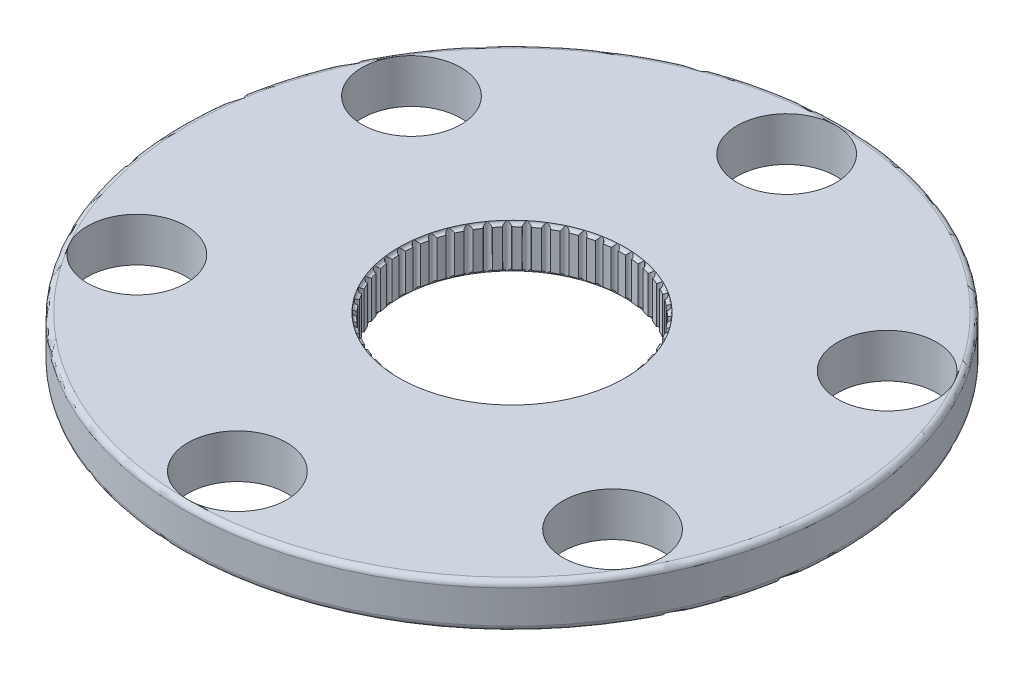
SolidWorks part; units mm, degrees
ref_plane "Front Plane" through (0, 0, 0) normal (0, 0, 1) x (1, 0, 0)
ref_plane "Top Plane" through (0, 0, 0) normal (0, 1, 0) x (1, 0, 0)
ref_plane "Right Plane" through (0, 0, 0) normal (1, 0, 0) x (0, 0, -1)
sketch "Sketch2" plane through (0, 0, 0) normal (0, 1, 0) x (1, 0, 0)
  line L0 (0, 73.1777) -> (0, -72.5679) construction
  line L1 (-73.7875, 0) -> (64.0305, 0) construction
  circle A0 centre (0, 0) radius 150
  circle A1 centre (0, 0) radius 50
  circle A2 centre (0, 125) radius 22.5
  circle A3 centre (108.2532, 62.5) radius 22.5
  circle A4 centre (108.2532, -62.5) radius 22.5
  circle A5 centre (0, -125) radius 22.5
  circle A6 centre (-108.2532, -62.5) radius 22.5
  circle A7 centre (-108.2532, 62.5) radius 22.5
  point P23 (0, 0)
  dimension "D1" = 100
  dimension "D2" = 300
  dimension "D3" = 45
  dimension "D4" = 125
  dimension "D5" = 6
extrude "Boss-Extrude1" add sketch "Sketch2" along normal mid plane 20
sketch "Sketch3" plane through (0, 0, 0) normal (1, 0, 0) x (0, 0, -1)
  line L0 (0, 0) -> (0, 49.9706) construction
  circle A0 centre (-50, 10) radius 1.5
  circle A1 centre (-50, -10) radius 1.5
  dimension "D1" = 3
  dimension "D2" = 3
revolve "Cut-Revolve1" cut sketch "Sketch3" angle 360 about L0
sketch "Sketch4" plane through (0, 0, 0) normal (0, 1, 0) x (1, 0, 0)
  circle A0 centre (-50, 0) radius 1.5
  circle A1 centre (0, 0) radius 50 construction
  dimension "D1" = 3
extrude "Cut-Extrude1" cut sketch "Sketch4" against normal through all both and the other way through all
pattern_circular "CirPattern1" count 50 over 360 about axis through (0, 8.5, 0) along (0, 1, 0) of "Cut-Extrude1"
fillet "Fillet1" radius 2.5 2 edges at (0, -10, 150) (0, 10, 150)
